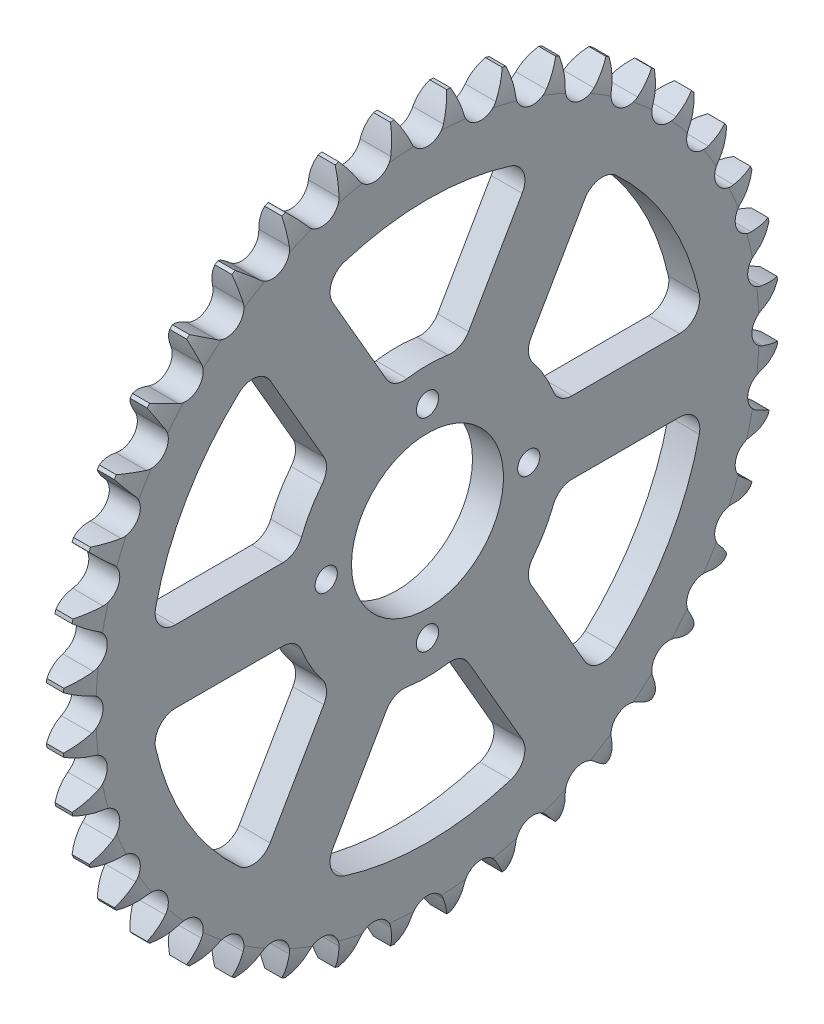
SolidWorks part; units mm, degrees
ref_plane "Plane1" through (0, 0, 0) normal (0, 0, 1) x (1, 0, 0)
ref_plane "Plane2" through (0, 0, 0) normal (0, 1, 0) x (1, 0, 0)
ref_plane "Plane3" through (0, 0, 0) normal (1, 0, 0) x (0, 0, -1)
sketch "Clipboard" plane through (0, 0, 0) normal (0, 1, 0) x (1, 0, 0)
  line L0 (0, 0) -> (12.161, -10.2043)
  line L1 (-15, 0) -> (100, 0) construction
  line L2 (0, 0) -> (-1.3675, 1.5456)
  line L3 (0, 0) -> (-14.8288, 5.6677)
  line L4 (0, 0) -> (2.3747, 1.9926)
  line L5 (0, 0) -> (-46.8476, -17.4728)
  line L6 (0, 0) -> (-7.5995, -5.1274)
  line L7 (-1.3675, 1.5456) -> (36.3683, 34.3489)
  line L8 (-76.2, 38.1) -> (-72.4, 38.1)
  line L9 (-73.5647, 42.6244) -> (-72.9723, 42.72)
  line L10 (-74, 16.2756) -> (-57.41, 16.2756)
  circle A0 centre (0, 0) radius 5.08
  circle A1 centre (0, 0) radius 37.5
  circle A2 centre (0, 0) radius 37.5
  dimension "Num_teeth" = 40
  dimension "Thickness" = 9.1675
sketch "BasProSke" plane through (0, 0, 0) normal (0, 1, 0) x (1, 0, 0)
  line L0 (-10, 0) -> (60, 0) construction
  line L1 (0, 0) -> (0, 98.182)
  line L2 (0, 0) -> (9.1675, 0)
  line L3 (9.1675, 0) -> (9.1675, 98.182)
  line L4 (7.1037, 106.0092) -> (2.0637, 106.0092)
  arc A0 (0, 98.182) -> (2.0637, 106.0092) centre (15.875, 98.182) cw
  arc A1 (9.1675, 98.182) -> (7.1037, 106.0092) centre (-6.7075, 98.182) ccw
  dimension "D1" = 15.875
  dimension "Thickness" = 9.1675
  dimension "Diameter" = 212.0185
revolve "Base-Revolve" add sketch "BasProSke" angle 360 about L0
sketch "TooCutSke" plane through (0, 0, 0) normal (1, 0, 0) x (0, 0, -1)
  line L0 (0, 101.2182) -> (4.786, 99.369) construction
  line L1 (0, 0) -> (0, 107) construction
  line L2 (0, 101.2182) -> (-10, 101.2182) construction
  line L3 (0, 101.2182) -> (-4.786, 99.369) construction
  arc A0 (4.786, 99.369) -> (8.027, 106.2063) centre (52.5511, 80.914) cw
  arc A1 (4.786, 99.369) -> (-4.786, 99.369) centre (0, 101.2182) cw
  arc A2 (-4.786, 99.369) -> (-8.027, 106.2063) centre (-52.5511, 80.914) ccw
  arc A3 (8.027, 106.2063) -> (-8.027, 106.2063) centre (0, 0) ccw
extrude "ToothCut" cut sketch "TooCutSke" along normal through all
pattern_circular "TeethCuts" count 40 every 9 about axis through (-10, 0, 0) along (1, 0, 0) of "ToothCut"
sketch "HubNeaOneSke" plane through (0, 0, 0) normal (-1, 0, 0) x (0, 0, 1)
  circle A0 centre (0, 0) radius 37.5
  dimension "Diameter" = 75
extrude "HubNearOne" [suppressed] add sketch "HubNeaOneSke" along normal blind 40.833
fillet "HubNearOneFillet" [suppressed] radius 0.6
sketch "HubNeaBotSke" plane through (0, 0, 0) normal (-1, 0, 0) x (0, 0, 1)
  circle A0 centre (0, 0) radius 37.5
  dimension "Diameter" = 75
extrude "HubNearBoth" [suppressed] add sketch "HubNeaBotSke" along normal blind 20.4165
fillet "HubNearBothFillet" [suppressed] radius 0.6
ref_plane "FarPln" through (9.1675, 0, 0) normal (1, 0, 0) x (0, 0, -1)
sketch "HubFarSke" plane through (9.1675, 0, 0) normal (1, 0, 0) x (0, 0, -1)
  circle A0 centre (0, 0) radius 37.5
  dimension "Diameter" = 75
extrude "HubFar" [suppressed] add sketch "HubFarSke" along normal blind 20.4165
fillet "HubFarFillet" [suppressed] radius 0.6
sketch "BorSke" plane through (0, 0, 0) normal (1, 0, 0) x (0, 0, -1)
  circle A0 centre (0, 0) radius 22.5
  dimension "Diameter" = 45
extrude "Bore" cut sketch "BorSke" along normal mid plane 100.001
sketch "KeySke" plane through (0, 0, 0) normal (1, 0, 0) x (0, 0, -1)
  line L0 (-7, 0) -> (-7, 26.3)
  line L1 (-7, 26.3) -> (7, 26.3)
  line L2 (7, 26.3) -> (7, 0)
  line L3 (0, 0) -> (0, 34) construction
  line L4 (-7, 0) -> (7, 0)
  dimension "Width" = 14
extrude "Keyway" [suppressed] cut sketch "KeySke" along normal mid plane 100.001
pattern_circular "Keyway2" [suppressed] count 2 every 90 about axis through (-10, 0, 0) along (1, 0, 0) reverse direction yes
sketch "Sketch1" plane through (9.1675, 0, 0) normal (1, 0, 0) x (0, 0, -1)
  line L0 (0, 0) -> (0, 106.6984) construction
  line L1 (0, 0) -> (58.1878, 100.7843) construction
  line L2 (10, 38.7298) -> (31.6308, 76.1954)
  line L3 (-10, 38.7298) -> (-31.6308, 76.1954)
  line L4 (38.541, 10.7047) -> (81.8026, 10.7047)
  line L5 (28.541, 28.0252) -> (50.1718, 65.4908)
  line L6 (28.541, -28.0252) -> (50.1718, -65.4908)
  line L7 (38.541, -10.7047) -> (81.8026, -10.7047)
  line L8 (-10, -38.7298) -> (-31.6308, -76.1954)
  line L9 (10, -38.7298) -> (31.6308, -76.1954)
  line L10 (-38.541, -10.7047) -> (-81.8026, -10.7047)
  line L11 (-28.541, -28.0252) -> (-50.1718, -65.4908)
  line L12 (-28.541, 28.0252) -> (-50.1718, 65.4908)
  line L13 (-38.541, 10.7047) -> (-81.8026, 10.7047)
  circle A0 centre (0, 0) radius 40
  circle A1 centre (0, 0) radius 82.5
  point P33 (0, 0)
  dimension "D1" = 80
  dimension "D3" = 165
  dimension "D2" = 30
  dimension "D4" = 20
  dimension "D5" = 6
extrude "Cut-Extrude2" cut sketch "Sketch1" against normal blind 10 contours L12 A1 L13 A0 | L2 A1 L3 A0 | L4 A1 L5 A0 | L6 A1 L7 A0 | L8 A1 L9 A0 | L10 A1 L11 A0 region at (9.1675, 63.5753, 0) region at (9.1675, 31.7877, -55.0578) region at (9.1675, 31.7877, 55.0578) region at (9.1675, -31.7877, -55.0578) region at (9.1675, -31.7877, 55.0578) region at (9.1675, -63.5753, 0)
fillet "Fillet1" radius 6 24 edges at (4.5837, 76.1954, 31.6308) (4.5837, 76.1954, -31.6308) (4.5837, 38.7298, 10) (4.5837, 38.7298, -10) (4.5837, 28.0252, -28.541) (4.5837, 10.7047, -38.541) (4.5837, 10.7047, -81.8026) (4.5837, 65.4908, -50.1718) (4.5837, -65.4908, -50.1718) (4.5837, -10.7047, -81.8026) (4.5837, -10.7047, -38.541) (4.5837, -28.0252, -28.541) (4.5837, -76.1954, 31.6308) (4.5837, -76.1954, -31.6308) (4.5837, -38.7298, 10) (4.5837, -38.7298, -10) (4.5837, -28.0252, 28.541) (4.5837, -10.7047, 38.541) (4.5837, -10.7047, 81.8026) (4.5837, -65.4908, 50.1718) (4.5837, 10.7047, 81.8026) (4.5837, 65.4908, 50.1718) (4.5837, 10.7047, 38.541) (4.5837, 28.0252, 28.541)
sketch "Sketch2" plane through (9.1675, 0, 0) normal (1, 0, 0) x (0, 0, -1)
  line L0 (0, 0) -> (30, 0) construction
  circle A0 centre (30, 0) radius 3.3
  circle A1 centre (0, -30) radius 3.3
  circle A2 centre (-30, 0) radius 3.3
  circle A3 centre (0, 30) radius 3.3
  point P13 (0, 0)
  dimension "D1" = 6.6
  dimension "D2" = 30
  dimension "D3" = 4
extrude "Cut-Extrude3" cut sketch "Sketch2" against normal blind 10
equation "' \"Pitch@Clipboard\" = 12.7"
equation "' \"Num_strands@Clipboard\" = 1"
equation "' \"Num_teeth@Clipboard\" = 9"
equation "' \"Hub_dia@Clipboard\" = 50"
equation "' \"Overall_len@Clipboard\" = 3"
equation "' \"Diameter@BorSke\" = 12"
equation "' \"T_dim@Clipboard\" = 1"
equation "' \"Width@KeySke\" = 2"
equation "' \"Dr@Clipboard\" = 8.51"
equation "' \"Face_width@Clipboard\" = 7.2"
equation "' \"Side_radius@Clipboard\" = 12.7"
equation "' \"Side_relief@Clipboard\" = 1.27"
equation "' \"Transv_pitch@Clipboard\" = 13.92"
equation "' \"Show_teeth@Clipboard\" = 9"
equation "' \"Fillet_rad@Clipboard\" = 0.6"
equation "' \"Plate_wid@Clipboard\" = 11.8"
equation "\"Num_teeth@Clipboard\" = int( \"Num_teeth@Clipboard\" )"
equation "\"Num_teeth@Clipboard\" = ((sgn( \"Num_teeth@Clipboard\" - 5.0)+1)*( \"Num_teeth@Clipboard\" - 5.0))/2 +5.0"
equation "\"Num_teeth@Clipboard\" = ((sgn( \"Num_teeth@Clipboard\" - 200.0)-1)*( \"Num_teeth@Clipboard\" - 200.0))/-2 +200.0"
equation "\"MHD@Clipboard\" = \"Pitch@Clipboard\" * (1.0 / tan(3.14159265 / \"Num_teeth@Clipboard\" )) - 1.04 * \"Plate_wid@Clipboard\" - 0.76"
equation "\"Thickness@Clipboard\"  = \"Face_width@Clipboard\" + (\"Num_strands@Clipboard\" - 1) * \"Transv_pitch@Clipboard\""
equation "\"OAL@Clipboard\" = \"Thickness@Clipboard\" + 2 * \"Fillet_rad@Clipboard\" + 1"
equation "\"MHD@Clipboard\" = ((sgn( \"MHD@Clipboard\" - \"Hub_dia@Clipboard\" )-1)*( \"MHD@Clipboard\" - \"Hub_dia@Clipboard\" ))/-2+ \"Hub_dia@Clipboard\""
equation "\"OAL@Clipboard\" = ((sgn( \"OAL@Clipboard\" - \"Overall_len@Clipboard\" )+1)*( \"OAL@Clipboard\" - \"Overall_len@Clipboard\" ))/2 + \"Overall_len@Clipboard\" + 0.0005"
equation "\"Num_teeth@TeethCuts\" = int( \"Show_teeth@Clipboard\" ) + 1"
equation "\"Num_teeth@TeethCuts\" = ((sgn( \"Num_teeth@TeethCuts\" - \"Num_teeth@Clipboard\" )-1)*( \"Num_teeth@TeethCuts\" - \"Num_teeth@Clipboard\" ))/-2+ \"Num_teeth@Clipboard\""
equation "\"Num_teeth@TeethCuts\" = ((sgn( \"Num_teeth@TeethCuts\" - 2.0)+1)*( \"Num_teeth@TeethCuts\" - 2.0))/2 +2.0"
equation "\"Angle@TeethCuts\" = 360.0 / \"Num_teeth@Clipboard\""
equation "\"Seat_radius@TooCutSke\" = ( \"Pitch@Clipboard\" / 2.0) / sin(3.14159265 / \"Num_teeth@Clipboard\" ) - \"Dr@Clipboard\" / 2.0 + \"Dr@Clipboard\" * 0.505"
equation "\"R1@TooCutSke\"  = \"Dr@Clipboard\" * 0.505"
equation "\"X@TooCutSke\" = 140.0 - (90.0 / \"Num_teeth@Clipboard\")"
equation "\"R2@TooCutSke\" = 0.12 * \"Dr@Clipboard\" * ( \"Num_teeth@Clipboard\" + 2.0)"
equation "\"Overcut@TooCutSke\" = 0.5 + 0.625 * \"Pitch@Clipboard\" - 0.5 * \"Dr@Clipboard\"  +  \"Pitch@Clipboard\" / 2.0 / sin(3.14159265 / \"Num_teeth@Clipboard\" )"
equation "\"Diameter@BasProSke\" = 2.0 * ( 0.625 * \"Pitch@Clipboard\" - 0.5 * \"Dr@Clipboard\"  +  \"Pitch@Clipboard\" / 2.0 / sin(3.14159265 / \"Num_teeth@Clipboard\" ))"
equation "\"Thickness@BasProSke\"  = \"Thickness@Clipboard\""
equation "\"G1@BasProSke\" =  \"Side_relief@Clipboard\""
equation "\"G2@BasProSke\" =  \"Side_relief@Clipboard\""
equation "\"D1@BasProSke\" =  \"Side_radius@Clipboard\""
equation "\"Diameter@HubNeaOneSke\" = \"MHD@Clipboard\""
equation "\"Length@HubNearOne\" = \"OAL@Clipboard\" - \"Thickness@BasProSke\""
equation "\"Diameter@HubNeaBotSke\" = \"MHD@Clipboard\""
equation "\"Length@HubNearBoth\" = ( \"OAL@Clipboard\" - \"Thickness@BasProSke\" ) / 2.0"
equation "\"D1@HubNearOneFillet\" = \"Fillet_rad@Clipboard\""
equation "\"D1@HubNearBothFillet\" = \"Fillet_rad@Clipboard\""
equation "\"Thickness@FarPln\" = \"Thickness@BasProSke\""
equation "\"Diameter@HubFarSke\" = \"MHD@Clipboard\""
equation "\"Length@HubFar\" = ( \"OAL@Clipboard\" - \"Thickness@BasProSke\" ) / 2.0"
equation "\"D1@HubFarFillet\" = \"Fillet_rad@Clipboard\""
equation "\"D1@Bore\" = \"OAL@Clipboard\" * 2.0"
equation "\"D1@Keyway\" = \"OAL@Clipboard\" * 2.0"
equation "\"Offset@KeySke\" = \"T_dim@Clipboard\" + \"Diameter@BorSke\" / 2.0"
